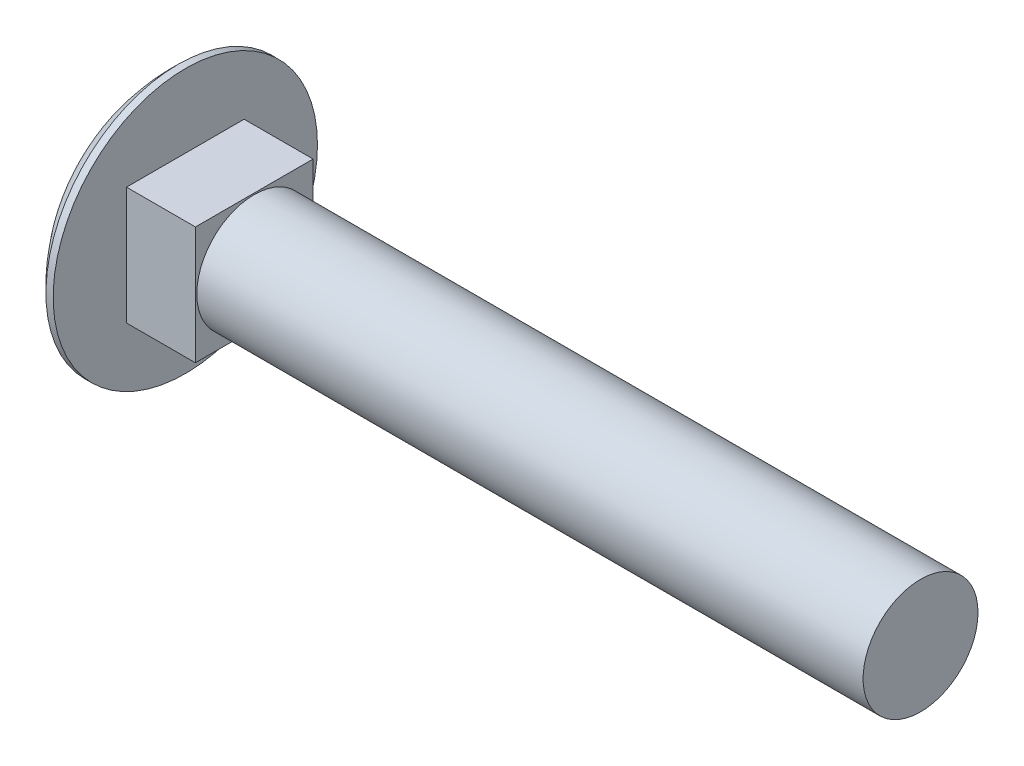
SolidWorks part; units mm, degrees
material "AISI 304 Stainless Steel"
ref_plane "Front Plane" through (0, 0, 0) normal (0, 0, 1) x (1, 0, 0)
ref_plane "Top Plane" through (0, 0, 0) normal (0, 1, 0) x (1, 0, 0)
ref_plane "Right Plane" through (0, 0, 0) normal (1, 0, 0) x (0, 0, -1)
ref_axis "Axis1" through (0, 0, -88.99) along (0, 0, 1)
sketch "Sketch1" plane through (0, 0, 0) normal (0, 0, 1) x (1, 0, 0)
  line L0 (3.9704, 9.1313) -> (4.4704, 9.1313)
  line L1 (4.4704, 9.1313) -> (4.4704, 3.81)
  line L2 (9.2329, 3.9688) -> (55.2704, 3.9688)
  line L3 (55.2704, 3.9688) -> (55.2704, 0)
  line L4 (55.2704, 0) -> (0, 0)
  line L5 (4.4704, 3.81) -> (9.2329, 3.81)
  line L6 (0, 0) -> (-6.2855, 0) construction
  line L7 (9.2329, 3.81) -> (9.2329, 3.9688)
  arc A0 (0, 0) -> (3.9704, 9.1313) centre (12.4855, 0) cw
  dimension "THREADED_DIA" = 7.9375
  dimension "THREADED_LENGTH" = 50.8
  dimension "NECK_LENGTH" = 4.7625
  dimension "HEAD_HEIGHT" = 4.4704
  dimension "D5" = 7.62
  dimension "D6" = 0.5
  dimension "HEAD_RADIUS" = 18.2626
revolve "Revolve1" add sketch "Sketch1" angle 360 about L6
sketch "Sketch2" plane through (4.4704, 0, 0) normal (1, 0, 0) x (0, 0, -1)
  line L1 (4.064, -4.064) -> (-4.064, -4.064)
  line L2 (4.064, -4.064) -> (4.064, 4.064)
  line L3 (4.064, 4.064) -> (-4.064, 4.064)
  line L4 (-4.064, -4.064) -> (-4.064, 4.064)
  line L5 (4.064, -4.064) -> (-4.064, 4.064) construction
  line L6 (4.064, 4.064) -> (-4.064, -4.064) construction
  point P0 (0, 0)
  dimension "NECK_WIDTH" = 8.128
extrude "Boss-Extrude1" add sketch "Sketch2" along normal up to surface (4.7625 mm away) up to face at (9.2329, 0, -3.81)
